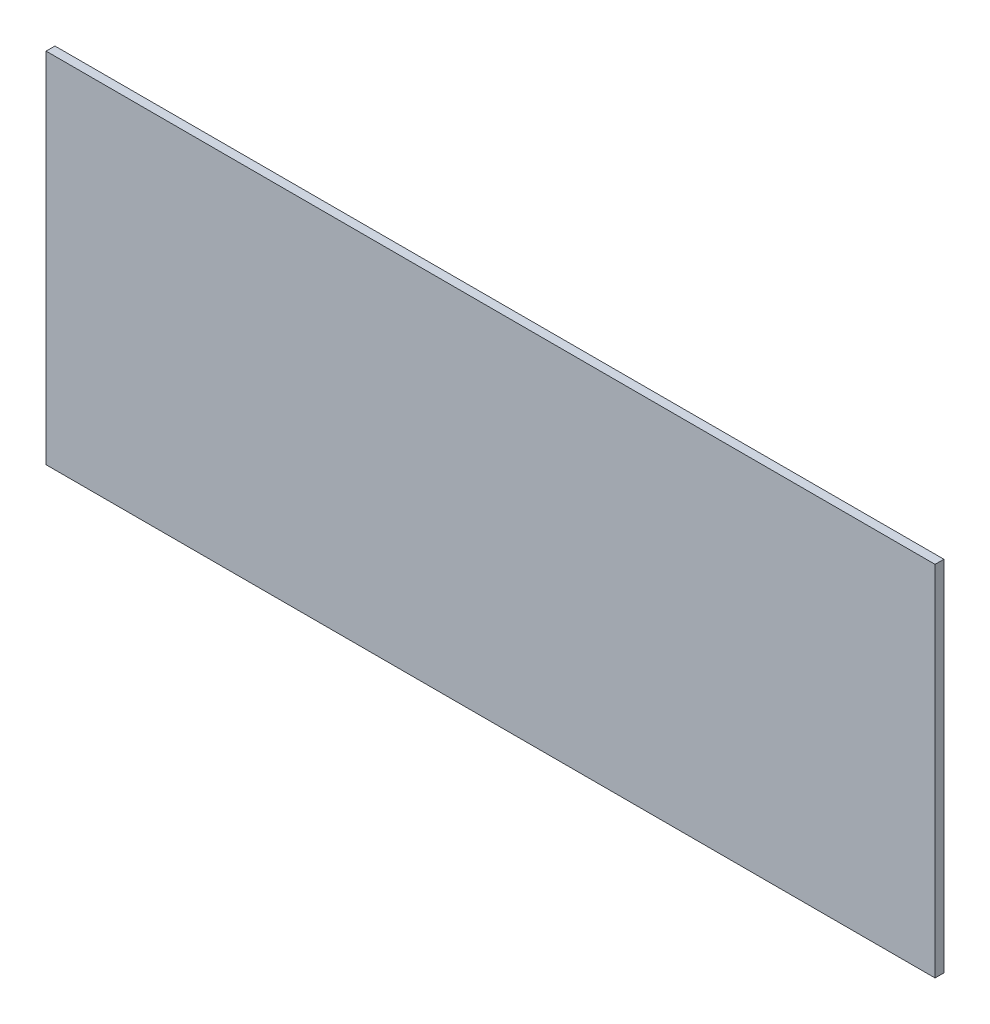
SolidWorks part; units mm, degrees
material "Eiche"
ref_plane "Ebene vorne" through (0, 0, 0) normal (0, 0, 1) x (1, 0, 0)
ref_plane "Ebene oben" through (0, 0, 0) normal (0, 1, 0) x (1, 0, 0)
ref_plane "Ebene rechts" through (0, 0, 0) normal (1, 0, 0) x (0, 0, -1)
sketch "Skizze1" plane through (0, 0, 0) normal (0, 0, 1) x (1, 0, 0)
  line L1 (0, 0) -> (10050, 0)
  line L2 (0, 0) -> (0, 4050)
  line L3 (0, 4050) -> (10050, 4050)
  line L4 (10050, 0) -> (10050, 4050)
  dimension "D1" = 10050
  dimension "D2" = 4050
extrude "Aufsatz-Linear austragen1" add sketch "Skizze1" along normal blind 100
